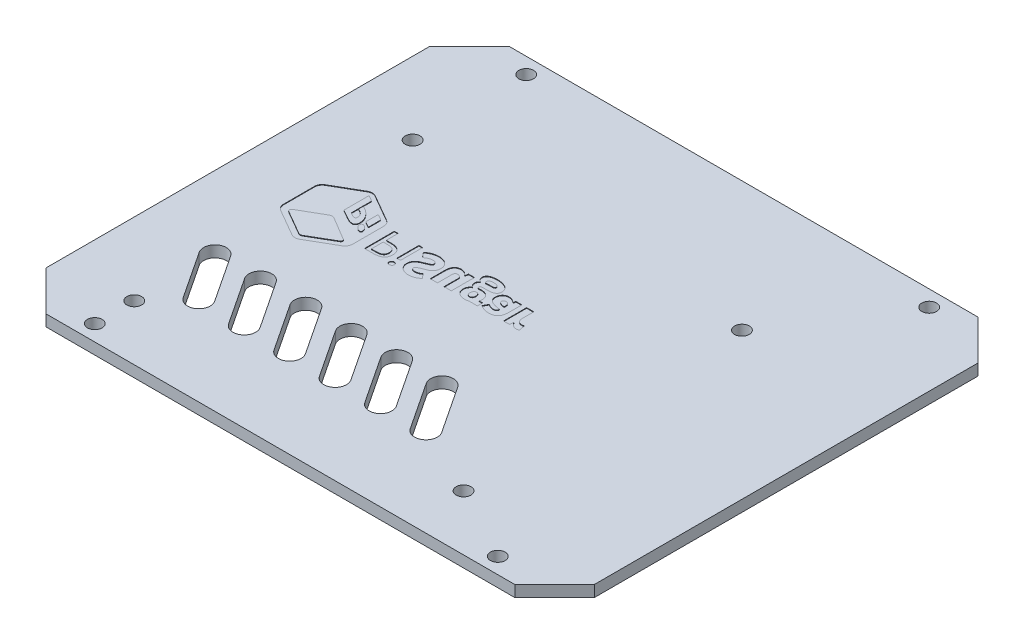
SolidWorks part; units mm, degrees
ref_plane "前视基准面" through (0, 0, 0) normal (0, 0, 1) x (1, 0, 0)
ref_plane "上视基准面" through (0, 0, 0) normal (0, 1, 0) x (1, 0, 0)
ref_plane "右视基准面" through (0, 0, 0) normal (1, 0, 0) x (0, 0, -1)
sketch "草图1" plane through (0, -19.39, 0) normal (0, -1, 0) x (1, 0, 0)
  line L16 (-51.8, -40.2958) -> (-44.7958, -47.3)
  line L17 (-44.7958, -47.3) -> (37.7958, -47.3)
  line L18 (37.7958, -47.3) -> (44.8, -40.2958)
  line L19 (44.8, -40.2958) -> (44.8, 27.2958)
  line L20 (44.8, 27.2958) -> (37.7958, 34.3)
  line L21 (-51.8, 27.2958) -> (-51.8, -40.2958)
  line L22 (37.7958, 34.3) -> (-44.7958, 34.3)
  line L23 (-44.7958, 34.3) -> (-51.8, 27.2958)
  line L24 (-51.8, -40.2958) -> (-44.7958, -47.3)
  line L25 (-44.7958, -47.3) -> (37.7958, -47.3)
  line L26 (37.7958, -47.3) -> (44.8, -40.2958)
  line L27 (44.8, -40.2958) -> (44.8, 27.2958)
  line L28 (44.8, 27.2958) -> (37.7958, 34.3)
  line L29 (-51.8, 27.2958) -> (-51.8, -40.2958)
  line L30 (37.7958, 34.3) -> (-44.7958, 34.3)
  line L31 (-44.7958, 34.3) -> (-51.8, 27.2958)
  dimension "D1" = 0.2
extrude "凸台-拉伸1" add sketch "草图1" along normal blind 2
sketch "草图2" plane through (0, -21.39, 0) normal (0, -1, 0) x (1, 0, 0)
  circle A0 centre (-39.0116, -24.5) radius 1.3
  circle A1 centre (19, -24.5) radius 1.3
  circle A2 centre (-39.0116, 24.5352) radius 1.3
  circle A3 centre (19, 24.5352) radius 1.3
  dimension "D1" = 2.6
extrude "切除-拉伸1" cut sketch "草图2" against normal up to next
sketch "草图3" plane through (0, -21.39, 0) normal (0, -1, 0) x (1, 0, 0)
  circle A0 centre (32, -44.5) radius 1.3 construction
  circle A1 centre (-39, -44.5) radius 1.3 construction
  circle A2 centre (32, 31.5) radius 1.3 construction
  circle A3 centre (-39, 31.5) radius 1.3 construction
  circle A4 centre (32, -44.5) radius 1.3
  circle A5 centre (-39, -44.5) radius 1.3
  circle A6 centre (32, 31.5) radius 1.3
  circle A7 centre (-39, 31.5) radius 1.3
extrude "切除-拉伸2" cut sketch "草图3" against normal up to next
sketch "草图4" plane through (0, -21.39, 0) normal (0, -1, 0) x (1, 0, 0)
  line L0 (-38.9928, 31.6194) -> (-39.0044, 24.6546) construction
  line L1 (-39.0282, 10.3) -> (-33.5143, 18.6425) construction
  line L2 (-40.6967, 11.4028) -> (-35.1828, 19.7453)
  line L3 (-37.3597, 9.1972) -> (-31.8458, 17.5397)
  line L5 (37.7958, 34.3) -> (-44.7958, 34.3) construction
  line L6 (-31.0282, 10.3) -> (-25.5143, 18.6425) construction
  line L9 (-32.6967, 11.4028) -> (-27.1828, 19.7453)
  line L12 (-29.3597, 9.1972) -> (-23.8458, 17.5397)
  line L15 (-23.0282, 10.3) -> (-17.5143, 18.6425) construction
  line L18 (-24.6967, 11.4028) -> (-19.1828, 19.7453)
  line L21 (-21.3597, 9.1972) -> (-15.8458, 17.5397)
  line L22 (-15.0282, 10.3) -> (-9.5143, 18.6425) construction
  line L23 (-16.6967, 11.4028) -> (-11.1828, 19.7453)
  line L24 (-13.3597, 9.1972) -> (-7.8458, 17.5397)
  line L25 (-7.0282, 10.3) -> (-1.5143, 18.6425) construction
  line L26 (-8.6967, 11.4028) -> (-3.1828, 19.7453)
  line L27 (-5.3597, 9.1972) -> (0.1542, 17.5397)
  line L28 (0.9718, 10.3) -> (6.4857, 18.6425) construction
  line L29 (-0.6967, 11.4028) -> (4.8172, 19.7453)
  line L30 (2.6403, 9.1972) -> (8.1542, 17.5397)
  arc A0 (-40.6967, 11.4028) -> (-37.3597, 9.1972) centre (-39.0282, 10.3) ccw
  arc A1 (-31.8458, 17.5397) -> (-35.1828, 19.7453) centre (-33.5143, 18.6425) ccw
  arc A12 (-32.6967, 11.4028) -> (-29.3597, 9.1972) centre (-31.0282, 10.3) ccw
  arc A13 (-23.8458, 17.5397) -> (-27.1828, 19.7453) centre (-25.5143, 18.6425) ccw
  arc A14 (-24.6967, 11.4028) -> (-21.3597, 9.1972) centre (-23.0282, 10.3) ccw
  arc A15 (-15.8458, 17.5397) -> (-19.1828, 19.7453) centre (-17.5143, 18.6425) ccw
  arc A16 (-16.6967, 11.4028) -> (-13.3597, 9.1972) centre (-15.0282, 10.3) ccw
  arc A17 (-7.8458, 17.5397) -> (-11.1828, 19.7453) centre (-9.5143, 18.6425) ccw
  arc A18 (-8.6967, 11.4028) -> (-5.3597, 9.1972) centre (-7.0282, 10.3) ccw
  arc A19 (0.1542, 17.5397) -> (-3.1828, 19.7453) centre (-1.5143, 18.6425) ccw
  arc A20 (-0.6967, 11.4028) -> (2.6403, 9.1972) centre (0.9718, 10.3) ccw
  arc A21 (8.1542, 17.5397) -> (4.8172, 19.7453) centre (6.4857, 18.6425) ccw
  point P6 (-36.2713, 14.4713)
  point P15 (-28.2713, 14.4713)
  point P22 (-20.2713, 14.4713)
  point P29 (-12.2713, 14.4713)
  point P36 (-4.2713, 14.4713)
  point P43 (3.7287, 14.4713)
  dimension "D1" = 2
  dimension "D2" = 10
  dimension "D3" = 5.5
  dimension "D4" = 12.8
  dimension "D5" = 24
  dimension "D6" = 6
extrude "切除-拉伸3" cut sketch "草图4" against normal up to next
sketch "草图5" plane through (0, -21.39, 0) normal (0, -1, 0) x (1, 0, 0)
  point P0 (-34.5006, 0.7543)
sketch_block_instance "块1-1"
sketch_block "块1"
sketch "草图6" plane through (0, -19.39, 0) normal (0, 1, 0) x (1, 0, 0)
  line L0 (-39.0322, 2.6968) -> (-34.8198, 0.2624) construction
  line L1 (-34.177, 0.2624) -> (-29.9873, 2.7014) construction
  line L2 (-29.9828, 3.2622) -> (-34.0539, 5.6966) construction
  line L3 (-29.6682, 9.5398) -> (-30.5435, 10.0367) construction
  line L4 (-30.6757, 9.9592) -> (-30.6757, 7.9487) construction
  line L5 (-30.6301, 7.8712) -> (-29.7548, 7.3788) construction
  line L6 (-29.6226, 7.4564) -> (-29.6226, 9.4623) construction
  line L7 (-33.3108, 9.1249) -> (-33.3108, 8.049) construction
  line L8 (-33.2652, 7.9715) -> (-32.8731, 7.7527) construction
  line L9 (-32.8458, 9.0109) -> (-33.2652, 9.2207) construction
  line L10 (-33.2652, 9.2207) -> (-33.2652, 10.0868) construction
  line L11 (-32.791, 9.8224) -> (-33.2652, 10.0868) construction
  line L12 (-34.3274, 7.7345) -> (-32.823, 6.8819) construction
  line L13 (-34.373, 12.0335) -> (-34.373, 7.8119) construction
  line L14 (-33.3563, 11.6095) -> (-34.2408, 12.111) construction
  line L15 (-33.3108, 10.1644) -> (-33.3108, 11.532) construction
  line L16 (-33.3108, 9.1249) -> (-33.3108, 10.1644) construction
  line L17 (-17.9609, 5.9474) -> (-18.6265, 5.6829) construction
  line L18 (-17.7011, 5.0538) -> (-17.0627, 4.2514) construction
  line L19 (-19.6477, 6.6221) -> (-18.9684, 6.9093) construction
  line L20 (-20.2085, 7.429) -> (-20.9333, 8.3134) construction
  line L21 (-10.1469, 9.1523) -> (-9.7593, 9.1523) construction
  line L22 (-5.5196, 7.1144) -> (-5.5196, 7.7664) construction
  line L23 (-26.0439, 6.3576) -> (-26.0439, 4.2651) construction
  line L24 (-26.0439, 4.2651) -> (-25.2871, 4.2651) construction
  line L25 (-25.2597, 6.3576) -> (-26.0439, 6.3576) construction
  line L26 (-26.7095, 3.7272) -> (-26.7095, 8.979) construction
  line L27 (-26.7095, 8.979) -> (-26.0439, 8.979) construction
  line L28 (-26.0439, 8.979) -> (-26.0439, 6.8956) construction
  line L29 (-26.0439, 6.8956) -> (-25.1731, 6.8956) construction
  line L30 (-25.2096, 3.7272) -> (-26.7095, 3.7272) construction
  line L31 (-33.1558, -0.189) -> (-33.8122, -0.5719) construction
  line L32 (-35.189, -0.5719) -> (-35.8455, -0.189) construction
  line L33 (-35.8455, -0.189) -> (-39.2511, 1.7759) construction
  line L34 (-39.2511, 1.7759) -> (-39.9076, 2.1543) construction
  line L35 (-40.596, 3.3442) -> (-40.596, 8.7967) construction
  line L36 (-39.9076, 9.9866) -> (-39.2511, 10.365) construction
  line L37 (-39.2511, 10.365) -> (-35.8455, 12.3299) construction
  line L38 (-35.8455, 12.3299) -> (-35.189, 12.7128) construction
  line L39 (-33.8122, 12.7128) -> (-33.1558, 12.3299) construction
  line L40 (-33.1558, 12.3299) -> (-29.7503, 10.365) construction
  line L41 (-29.7503, 10.365) -> (-29.0938, 9.9866) construction
  line L42 (-28.4054, 8.7967) -> (-28.4054, 3.3442) construction
  line L43 (-29.0938, 2.1543) -> (-29.7503, 1.7759) construction
  line L44 (-29.7503, 1.7759) -> (-33.1558, -0.189) construction
  line L45 (-5.3737, 8.5687) -> (-5.2826, 8.979) construction
  line L46 (-5.2826, 8.979) -> (-4.2431, 8.979) construction
  line L47 (-4.2431, 8.979) -> (-4.2431, 6.6631) construction
  line L48 (-7.6486, 5.3365) -> (-7.2018, 6.1753) construction
  line L49 (-5.4056, 8.5687) -> (-5.3737, 8.5687) construction
  line L50 (-8.0133, 5.8243) -> (-8.0133, 4.9034) construction
  line L51 (-8.0133, 4.9034) -> (-9.5086, 4.9034) construction
  line L52 (-11.3094, 7.3378) -> (-11.3094, 7.3652) construction
  line L53 (-11.3869, 8.8286) -> (-11.3869, 8.8651) construction
  line L54 (-9.5178, 8.1767) -> (-10.1606, 8.1767) construction
  line L55 (-8.6424, 5.8243) -> (-8.0133, 5.8243) construction
  line L56 (-13.8761, 4.9034) -> (-13.8761, 7.5749) construction
  line L57 (-15.0295, 7.2649) -> (-15.0295, 4.9034) construction
  line L58 (-15.0295, 4.9034) -> (-16.3014, 4.9034) construction
  line L59 (-16.3014, 4.9034) -> (-16.3014, 7.4245) construction
  line L60 (-13.7575, 8.4183) -> (-13.7302, 8.4183) construction
  line L61 (-13.7302, 8.4183) -> (-13.639, 8.979) construction
  line L62 (-13.639, 8.979) -> (-12.5996, 8.979) construction
  line L63 (-12.5996, 8.979) -> (-12.5996, 4.9034) construction
  line L64 (-12.5996, 4.9034) -> (-13.8761, 4.9034) construction
  line L65 (-21.7265, 8.979) -> (-21.7265, 5.0857) construction
  line L66 (-22.3785, 8.979) -> (-21.7265, 8.979) construction
  line L67 (-22.3785, 5.0857) -> (-22.3785, 8.979) construction
  line L68 (-21.7265, 5.0857) -> (-22.3785, 5.0857) construction
  line L69 (-3.4042, 8.979) -> (-2.1368, 8.979) construction
  line L70 (-2.1368, 8.979) -> (-2.1368, 6.6494) construction
  line L71 (-0.8102, 5.9838) -> (-0.596, 4.8851) construction
  line L72 (-2.2508, 5.61) -> (-2.2782, 5.61) construction
  line L73 (-2.2782, 5.61) -> (-2.3648, 4.9034) construction
  line L74 (-2.3648, 4.9034) -> (-3.4042, 4.9034) construction
  line L75 (-3.4042, 4.9034) -> (-3.4042, 8.979) construction
  line L76 (-39.0322, 2.6968) -> (-34.8198, 0.2624)
  line L77 (-34.177, 0.2624) -> (-29.9873, 2.7014)
  line L78 (-29.9828, 3.2622) -> (-34.0539, 5.6966)
  line L79 (-29.6682, 9.5398) -> (-30.5435, 10.0367)
  line L80 (-30.6757, 9.9592) -> (-30.6757, 7.9487)
  line L81 (-30.6301, 7.8712) -> (-29.7548, 7.3788)
  line L82 (-29.6226, 7.4564) -> (-29.6226, 9.4623)
  line L83 (-33.3108, 9.1249) -> (-33.3108, 8.049)
  line L84 (-33.2652, 7.9715) -> (-32.8731, 7.7527)
  line L85 (-32.8458, 9.0109) -> (-33.2652, 9.2207)
  line L86 (-33.2652, 9.2207) -> (-33.2652, 10.0868)
  line L87 (-32.791, 9.8224) -> (-33.2652, 10.0868)
  line L88 (-34.3274, 7.7345) -> (-32.823, 6.8819)
  line L89 (-34.373, 12.0335) -> (-34.373, 7.8119)
  line L90 (-33.3563, 11.6095) -> (-34.2408, 12.111)
  line L91 (-33.3108, 10.1644) -> (-33.3108, 11.532)
  line L92 (-33.3108, 9.1249) -> (-33.3108, 10.1644)
  line L93 (-17.9609, 5.9474) -> (-18.6265, 5.6829)
  line L94 (-17.7011, 5.0538) -> (-17.0627, 4.2514)
  line L95 (-19.6477, 6.6221) -> (-18.9684, 6.9093)
  line L96 (-20.2085, 7.429) -> (-20.9333, 8.3134)
  line L97 (-10.1469, 9.1523) -> (-9.7593, 9.1523)
  line L98 (-5.5196, 7.1144) -> (-5.5196, 7.7664)
  line L99 (-26.0439, 6.3576) -> (-26.0439, 4.2651)
  line L100 (-26.0439, 4.2651) -> (-25.2871, 4.2651)
  line L101 (-25.2597, 6.3576) -> (-26.0439, 6.3576)
  line L102 (-26.7095, 3.7272) -> (-26.7095, 8.979)
  line L103 (-26.7095, 8.979) -> (-26.0439, 8.979)
  line L104 (-26.0439, 8.979) -> (-26.0439, 6.8956)
  line L105 (-26.0439, 6.8956) -> (-25.1731, 6.8956)
  line L106 (-25.2096, 3.7272) -> (-26.7095, 3.7272)
  line L107 (-33.1558, -0.189) -> (-33.8122, -0.5719)
  line L108 (-35.189, -0.5719) -> (-35.8455, -0.189)
  line L109 (-35.8455, -0.189) -> (-39.2511, 1.7759)
  line L110 (-39.2511, 1.7759) -> (-39.9076, 2.1543)
  line L111 (-40.596, 3.3442) -> (-40.596, 8.7967)
  line L112 (-39.9076, 9.9866) -> (-39.2511, 10.365)
  line L113 (-39.2511, 10.365) -> (-35.8455, 12.3299)
  line L114 (-35.8455, 12.3299) -> (-35.189, 12.7128)
  line L115 (-33.8122, 12.7128) -> (-33.1558, 12.3299)
  line L116 (-33.1558, 12.3299) -> (-29.7503, 10.365)
  line L117 (-29.7503, 10.365) -> (-29.0938, 9.9866)
  line L118 (-28.4054, 8.7967) -> (-28.4054, 3.3442)
  line L119 (-29.0938, 2.1543) -> (-29.7503, 1.7759)
  line L120 (-29.7503, 1.7759) -> (-33.1558, -0.189)
  line L121 (-5.3737, 8.5687) -> (-5.2826, 8.979)
  line L122 (-5.2826, 8.979) -> (-4.2431, 8.979)
  line L123 (-4.2431, 8.979) -> (-4.2431, 6.6631)
  line L124 (-7.6486, 5.3365) -> (-7.2018, 6.1753)
  line L125 (-5.4056, 8.5687) -> (-5.3737, 8.5687)
  line L126 (-8.0133, 5.8243) -> (-8.0133, 4.9034)
  line L127 (-8.0133, 4.9034) -> (-9.5086, 4.9034)
  line L128 (-11.3094, 7.3378) -> (-11.3094, 7.3652)
  line L129 (-11.3869, 8.8286) -> (-11.3869, 8.8651)
  line L130 (-9.5178, 8.1767) -> (-10.1606, 8.1767)
  line L131 (-8.6424, 5.8243) -> (-8.0133, 5.8243)
  line L132 (-13.8761, 4.9034) -> (-13.8761, 7.5749)
  line L133 (-15.0295, 7.2649) -> (-15.0295, 4.9034)
  line L134 (-15.0295, 4.9034) -> (-16.3014, 4.9034)
  line L135 (-16.3014, 4.9034) -> (-16.3014, 7.4245)
  line L136 (-13.7575, 8.4183) -> (-13.7302, 8.4183)
  line L137 (-13.7302, 8.4183) -> (-13.639, 8.979)
  line L138 (-13.639, 8.979) -> (-12.5996, 8.979)
  line L139 (-12.5996, 8.979) -> (-12.5996, 4.9034)
  line L140 (-12.5996, 4.9034) -> (-13.8761, 4.9034)
  line L141 (-21.7265, 8.979) -> (-21.7265, 5.0857)
  line L142 (-22.3785, 8.979) -> (-21.7265, 8.979)
  line L143 (-22.3785, 5.0857) -> (-22.3785, 8.979)
  line L144 (-21.7265, 5.0857) -> (-22.3785, 5.0857)
  line L145 (-3.4042, 8.979) -> (-2.1368, 8.979)
  line L146 (-2.1368, 8.979) -> (-2.1368, 6.6494)
  line L147 (-0.8102, 5.9838) -> (-0.596, 4.8851)
  line L148 (-2.2508, 5.61) -> (-2.2782, 5.61)
  line L149 (-2.2782, 5.61) -> (-2.3648, 4.9034)
  line L150 (-2.3648, 4.9034) -> (-3.4042, 4.9034)
  line L151 (-3.4042, 4.9034) -> (-3.4042, 8.979)
  spline S0 degree 3 poles (1947.2043, 259.0221) (-2040.5975, -86.3945) (1971.5647, -86.1046) (-2015.9835, 259.8919) knots -24.014283 -24.014283 -24.014283 -24.014283 31.060476 31.060476 31.060476 31.060476 only from (-34.8198, 0.2624) to (-34.177, 0.2624) construction
  spline S1 degree 3 poles (-178.8618, 1996.4067) (-13.3017, -2002.4803) (85.7628, 2005.1657) (-277.1173, -1980.6649) knots -12.069605 -12.069605 -12.069605 -12.069605 23.053377 23.053377 23.053377 23.053377 only from (-29.9873, 2.7014) to (-29.9828, 3.2622) construction
  spline S2 degree 3 poles (-2011.9647, -280.5218) (1973.0796, 101.2598) (-2042.0834, 101.2623) (1942.99, -280.5143) knots -16.956312 -16.956312 -16.956312 -16.956312 31.955994 31.955994 31.955994 31.955994 only from (-34.0539, 5.6966) to (-34.9429, 5.6966) construction
  spline S3 degree 2 poles (1696.8938, 1005.9909) (-1772.9636, -998.1959) (1692.7429, 1003.6514) knots -19.544322 -19.544322 -19.544322 21.524182 21.524182 21.524182 only from (-34.9429, 5.6966) to (-39.0732, 3.3123) construction
  spline S4 degree 3 poles (312.9236, -1964.6822) (-255.5836, 1997.2947) (39.8207, -2001.4292) (20.6091, 2000.9771) knots -16.033039 -16.033039 -16.033039 -16.033039 19.060221 19.060221 19.060221 19.060221 only from (-39.0732, 3.3123) to (-39.0322, 2.6968) construction
  spline S5 degree 3 poles (1612.1466, 1139.1382) (-173.749, 124.6775) (-29.5451, -1.4055) (-29.5451, 6.2482) (-29.5451, 12.5795) (-131.1047, 41.0713) (891.7703, -1766.7786) knots -20.983072 -20.983072 -20.983072 -20.983072 3 3 3 23.1269 23.1269 23.1269 23.1269 only from (-30.1469, 6.0431) to (-30.1469, 7.1281) construction
  spline S6 degree 3 poles (-1593.6748, -1232.4433) (112.4759, -108.2288) (-30.7532, 14.45) (-30.7532, 6.9321) (-30.7532, 0.2328) (76.6581, -24.0346) (-1002.5668, 1752.6044) knots -22.899222 -22.899222 -22.899222 -22.899222 1 1 1 21.696321 21.696321 21.696321 21.696321 only from (-30.1469, 7.1281) to (-30.1469, 6.0431) construction
  spline S7 degree 3 poles (-1735.267, -1035.1971) (1720.3132, 981.2712) (-1822.079, -884.2768) (1795.5461, 824.5182) knots -24.864003 -24.864003 -24.864003 -24.864003 29.805716 29.805716 29.805716 29.805716 only from (-30.5435, 10.0367) to (-30.6757, 9.9592) construction
  spline S8 degree 3 poles (1803.8452, -787.8206) (-1835.1338, 879.7734) (1736.3613, -937.8925) (-1752.2845, 1025.0132) knots -52.644856 -52.644856 -52.644856 -52.644856 63.422153 63.422153 63.422153 63.422153 only from (-30.6757, 7.9487) to (-30.6301, 7.8712) construction
  spline S9 degree 3 poles (1675.9971, 1050.9308) (-1781.5786, -962.103) (1762.6814, 899.8753) (-1856.6746, -805.2277) knots -20.869425 -20.869425 -20.869425 -20.869425 33.809897 33.809897 33.809897 33.809897 only from (-29.7548, 7.3788) to (-29.6226, 7.4564) construction
  spline S10 degree 3 poles (-1017.153, 1748.416) (898.1967, -1765.8691) (-895.3334, 1815.971) (771.5167, -1822.726) knots -45.73326 -45.73326 -45.73326 -45.73326 46.535072 46.535072 46.535072 46.535072 only from (-29.6226, 9.4623) to (-29.6682, 9.5398) construction
  spline S11 degree 3 poles (1241.4728, -1544.2848) (-126.4363, -19.7603) (-21.5989, 9.5171) (-21.5989, 3.8639) (-21.5989, -3.1211) (-150.7291, 66.7677) (1747.5616, 931.244) knots -20.398043 -20.398043 -20.398043 -20.398043 3 3 3 28.967808 28.967808 28.967808 28.967808 only from (-22.0502, 4.2833) to (-22.0502, 3.44) construction
  spline S12 degree 3 poles (-1791.638, 931.233) (106.6275, 66.7672) (-22.5016, -3.1211) (-22.5016, 3.8639) (-22.5016, 9.5171) (82.3355, -19.7602) (-1285.567, -1544.2778) knots -24.967698 -24.967698 -24.967698 -24.967698 1 1 1 24.398007 24.398007 24.398007 24.398007 only from (-22.0502, 3.44) to (-22.0502, 4.2833) construction
  spline S13 degree 3 poles (953.112, -1731.5311) (-960.0271, 1783.9495) (831.3079, -1798.9714) (-833.3757, 1840.6921) knots -41.715469 -41.715469 -41.715469 -41.715469 50.515238 50.515238 50.515238 50.515238 only from (-33.3108, 8.049) to (-33.2652, 7.9715) construction
  spline S14 degree 3 poles (345.3515, -1953.7628) (-656.074, 2008.4671) (704.4049, -1945.0024) (-795.7723, 1856.1671) knots -18.836401 -18.836401 -18.836401 -18.836401 26.867419 26.867419 26.867419 26.867419 only from (-32.8731, 7.7527) to (-32.0799, 7.9031) construction
  spline S15 degree 3 poles (393.8329, 1947.428) (-1017.3565, -1766.8215) (1294.138, 1559.3727) (-1541.9229, -1298.5467) knots -37.738435 -37.738435 -37.738435 -37.738435 30.849118 30.849118 30.849118 30.849118 only from (-32.0799, 7.9031) to (-32.8458, 9.0109) construction
  spline S16 degree 3 poles (-1970.6267, 490.4514) (1900.3877, -652.3893) (-1909.3139, 822.203) (1735.9268, -921.8099) knots -2.984455 -2.984455 -2.984455 -2.984455 24.908291 24.908291 24.908291 24.908291 only from (-31.0405, 7.315) to (-32.791, 9.8224) construction
  spline S17 degree 3 poles (1301.0551, -1483.1694) (-1380.7778, 1570.3517) (1272.9624, -1585.6466) (-1251.2088, 1591.7607) knots -4.177868 -4.177868 -4.177868 -4.177868 21.267464 21.267464 21.267464 21.267464 only from (-32.823, 6.8819) to (-31.0405, 7.315) construction
  spline S18 degree 3 poles (-426.7908, -1953.0944) (416.9018, 1960.3516) (-543.6183, -1930.3492) (531.9657, 1925.7159) knots -40.574336 -40.574336 -40.574336 -40.574336 54.224541 54.224541 54.224541 54.224541 only from (-34.373, 7.8119) to (-34.3274, 7.7345) construction
  spline S19 degree 3 poles (-1739.7201, -1031.8845) (1717.3311, 982.0362) (-1826.4475, -880.8273) (1792.473, 825.1567) knots -21.867988 -21.867988 -21.867988 -21.867988 32.80886 32.80886 32.80886 32.80886 only from (-34.2408, 12.111) to (-34.373, 12.0335) construction
  spline S20 degree 3 poles (1326.5597, 1477.8337) (-1443.7748, -1422.5109) (1417.5131, 1403.8248) (-1515.2659, -1331.1895) knots -66.611259 -66.611259 -66.611259 -66.611259 68.63044 68.63044 68.63044 68.63044 only from (-33.3108, 11.532) to (-33.3563, 11.6095) construction
  spline S21 degree 3 poles (-1127.9465, 1668.9065) (1205.0665, -1581.8003) (-1320.6139, 1532.1331) (1326.4072, -1474.1074) knots -17.356672 -17.356672 -17.356672 -17.356672 19.212167 19.212167 19.212167 19.212167 only from (-18.6265, 5.6829) to (-19.4334, 5.0857) construction
  spline S22 degree 3 poles (1945.6237, -352.8331) (-1917.2958, 619.5498) (1753.4488, -897.6325) (-1594.6226, 1226.9154) knots -23.773694 -23.773694 -23.773694 -23.773694 31.399142 31.399142 31.399142 31.399142 only from (-19.4334, 5.0857) to (-18.7952, 4.6435) construction
  spline S23 degree 3 poles (-1957.8604, 491.3787) (1905.2875, -332.0334) (-1960.1859, 166.6666) (1980.2936, 44.6676) knots -22.175827 -22.175827 -22.175827 -22.175827 30.019969 30.019969 30.019969 30.019969 only from (-18.7952, 4.6435) to (-17.7011, 5.0538) construction
  spline S24 degree 3 poles (-1996.9289, 274.3391) (2008.3741, -55.5657) (-2041.9478, -141.8187) (1949.9756, 346.3582) knots -14.985955 -14.985955 -14.985955 -14.985955 26.624596 26.624596 26.624596 26.624596 only from (-17.0627, 4.2514) to (-18.7952, 3.5448) construction
  spline S25 degree 3 poles (-959.5674, 1764.5293) (1176.2874, -1603.5878) (-1432.6495, 1427.6748) (1567.7803, -1205.173) knots -7.558703 -7.558703 -7.558703 -7.558703 20.482777 20.482777 20.482777 20.482777 only from (-18.7952, 3.5448) to (-20.7327, 5.1587) construction
  spline S26 degree 3 poles (1924.0493, -458.54) (-2016.5165, 343.495) (1995.4741, -211.501) (-2016.1303, 116.1959) knots -7.852621 -7.852621 -7.852621 -7.852621 24.144848 24.144848 24.144848 24.144848 only from (-20.7327, 5.1587) to (-19.6477, 6.6221) construction
  spline S27 degree 3 poles (615.0637, -1888.8545) (-795.6899, 1841.0297) (868.9978, -1778.6578) (-986.0957, 1757.28) knots -9.138526 -9.138526 -9.138526 -9.138526 27.25787 27.25787 27.25787 27.25787 only from (-18.9684, 6.9093) to (-18.2162, 7.5111) construction
  spline S28 degree 3 poles (215.7009, 1986.9997) (-654.6592, -1923.8751) (894.6606, 1828.6602) (-1110.216, -1665.8008) knots -22.542702 -22.542702 -22.542702 -22.542702 37.658646 37.658646 37.658646 37.658646 only from (-18.2162, 7.5111) to (-18.9137, 7.9761) construction
  spline S29 degree 3 poles (-1605.429, -1208.7716) (1666.7814, 1140.7416) (-1773.5402, -1019.3674) (1765.9801, 905.5471) knots -8.791084 -8.791084 -8.791084 -8.791084 32.386114 32.386114 32.386114 32.386114 only from (-18.9137, 7.9761) to (-20.2085, 7.429) construction
  spline S30 degree 3 poles (1966.5787, -197.5818) (-2051.7497, -0.967) (2002.48, 224.4874) (-1974.8286, -400.794) knots -6.294928 -6.294928 -6.294928 -6.294928 33.756853 33.756853 33.756853 33.756853 only from (-20.9333, 8.3134) to (-18.9411, 9.0793) construction
  spline S31 degree 3 poles (124.1341, -1982.3989) (-457.1442, 1958.1164) (708.8959, -1855.2284) (-1015.0804, 1736.3895) knots 0.697384 0.697384 0.697384 0.697384 28.978211 28.978211 28.978211 28.978211 only from (-18.9411, 9.0793) to (-16.9033, 7.4108) construction
  spline S32 degree 3 poles (-1495.2544, 1354.2838) (1523.5493, -1377.9736) (-1538.1686, 1424.3054) (1353.4505, -1448.6746) knots -4.734801 -4.734801 -4.734801 -4.734801 40.265101 40.265101 40.265101 40.265101 only from (-16.9033, 7.4108) to (-17.9609, 5.9474) construction
  spline S33 degree 3 poles (-1961.8056, -418.0731) (126.6492, -101.6131) (-10.6711, 16.7967) (-10.6711, 6.2847) (-10.6711, -3.9538) (125.3735, 107.9903) (-1932.7785, 547.0377) knots -21.79377 -21.79377 -21.79377 -21.79377 3 3 3 27.67833 27.67833 27.67833 27.67833 only from (-10.156, 6.923) to (-10.156, 5.6556) construction
  spline S34 degree 3 poles (1882.1607, 641.7029) (-158.572, 123.862) (-9.6409, -4.6535) (-9.6409, 6.2847) (-9.6409, 17.5385) (-160.5965, -118.9677) (1923.9331, -488.0552) knots -25.364902 -25.364902 -25.364902 -25.364902 1 1 1 27.543492 27.543492 27.543492 27.543492 only from (-10.156, 5.6556) to (-10.156, 6.923) construction
  spline S35 degree 3 poles (398.3769, -1946.8651) (-621.0655, 1916.7975) (746.5301, -1849.6014) (-860.4662, 1818.6943) knots -20.367991 -20.367991 -20.367991 -20.367991 27.043685 27.043685 27.043685 27.043685 only from (-9.7593, 9.1523) to (-9.1667, 9.4441) construction
  spline S36 degree 3 poles (-1851.6901, 784.2948) (1770.8918, -932.7585) (-1685.1957, 1125.6418) (1512.1872, -1283.8884) knots -14.155704 -14.155704 -14.155704 -14.155704 26.455766 26.455766 26.455766 26.455766 only from (-9.1667, 9.4441) to (-10.0557, 9.8954) construction
  spline S37 degree 3 poles (-1999.7746, -177.9397) (2048.5506, 17.7992) (-2059.7856, 149.4036) (1971.6374, -249.0633) knots -24.53604 -24.53604 -24.53604 -24.53604 22.203045 22.203045 22.203045 22.203045 only from (-10.0557, 9.8954) to (-10.9219, 9.4668) construction
  spline S38 degree 3 poles (335.4233, 1977.3974) (-130.5762, -1935.4278) (-138.8194, 1950.0115) (386.7962, -1948.2187) knots -42.090152 -42.090152 -42.090152 -42.090152 46.007634 46.007634 46.007634 46.007634 only from (-10.9219, 9.4668) to (-10.7304, 9.1021) construction
  spline S39 degree 3 poles (-2000.164, -195.6542) (1968.231, 177.2652) (-1992.5781, -127.132) (1986.8184, 117.9013) knots -23.761314 -23.761314 -23.761314 -23.761314 27.411452 27.411452 27.411452 27.411452 only from (-10.7304, 9.1021) to (-10.1469, 9.1523) construction
  spline S40 degree 3 poles (1900.4815, 611.268) (-1853.5024, -713.4995) (1804.2956, 824.4669) (-1796.5625, -882.5407) knots -25.691977 -25.691977 -25.691977 -25.691977 25.491412 25.491412 25.491412 25.491412 only from (-5.5196, 7.7664) to (-6.135, 8.09) construction
  spline S41 degree 3 poles (-2003.4629, -52.8338) (2017.9029, -136.2777) (-2009.5197, 324.3726) (1939.2706, -450.8338) knots -29.27083 -29.27083 -29.27083 -29.27083 28.779665 28.779665 28.779665 28.779665 only from (-6.135, 8.09) to (-6.5727, 7.739) construction
  spline S42 degree 3 poles (-1965.4656, -395.4958) (1971.7383, 441.6954) (-1983.3474, -426.4496) (1951.4791, 419.1184) knots -18.272249 -18.272249 -18.272249 -18.272249 20.366917 20.366917 20.366917 20.366917 only from (-6.5727, 7.739) to (-5.5196, 7.1144) construction
  spline S43 degree 3 poles (-552.3477, -1916.0072) (39.6444, 1949.1893) (231.1798, -1947.9287) (-488.2476, 1949.0672) knots -16.951569 -16.951569 -16.951569 -16.951569 21.292276 21.292276 21.292276 21.292276 only from (-25.2871, 4.2651) to (-23.9011, 5.2681) construction
  spline S44 degree 3 poles (74.9674, -1978.7796) (-669.1868, 1491.4113) (1220.9961, -1007.5518) (-1925.4997, 576.7533) knots -20.703775 -20.703775 -20.703775 -20.703775 29.911591 29.911591 29.911591 29.911591 only from (-23.9011, 5.2681) to (-25.2597, 6.3576) construction
  spline S45 degree 3 poles (1967.7044, -102.3152) (-2083.6001, -202.2982) (1987.7708, 465.393) (-1913.3422, -643.1952) knots -12.662635 -12.662635 -12.662635 -12.662635 20.708978 20.708978 20.708978 20.708978 only from (-25.1731, 6.8956) to (-23.2401, 5.2681) construction
  spline S46 degree 3 poles (-1462.7137, 1393.5071) (1511.2501, -1404.3078) (-1580.4996, 1407.0991) (1432.7296, -1365.1759) knots -7.615095 -7.615095 -7.615095 -7.615095 23.693651 23.693651 23.693651 23.693651 only from (-23.2401, 5.2681) to (-25.2096, 3.7272) construction
  spline S47 degree 3 poles (-1986.2159, -424.6605) (1872.5149, 650.7296) (-1856.7008, -859.0204) (1668.1443, 1044.8861) knots -40.403395 -40.403395 -40.403395 -40.403395 46.454358 46.454358 46.454358 46.454358 only from (-33.8122, -0.5719) to (-34.5006, -0.7543) construction
  spline S48 degree 3 poles (-1740.3489, 1039.5921) (1790.0962, -854.0172) (-1943.0897, 646.2372) (1918.0006, -420.927) knots -38.373718 -38.373718 -38.373718 -38.373718 48.302597 48.302597 48.302597 48.302597 only from (-34.5006, -0.7543) to (-35.189, -0.5719) construction
  spline S49 degree 3 poles (-754.8971, 1867.8409) (885.9932, -1784.6) (-1157.7277, 1677.1962) (1246.9181, -1524.5355) knots -12.834285 -12.834285 -12.834285 -12.834285 29.798641 29.798641 29.798641 29.798641 only from (-39.9076, 2.1543) to (-40.596, 3.3442) construction
  spline S50 degree 3 poles (1310.7611, 1480.2732) (-1219.4015, -1620.1293) (943.9093, 1763.7167) (-807.2491, -1834.6442) knots -11.169927 -11.169927 -11.169927 -11.169927 32.277267 32.277267 32.277267 32.277267 only from (-40.596, 8.7967) to (-39.9076, 9.9866) construction
  spline S51 degree 3 poles (1829.5545, -704.5958) (-1983.3127, 518.655) (1959.6502, -271.0062) (-2031.7382, 64.4568) knots -28.630568 -28.630568 -28.630568 -28.630568 59.634843 59.634843 59.634843 59.634843 only from (-35.189, 12.7128) to (-34.5006, 12.8952) construction
  spline S52 degree 3 poles (1962.7022, 65.7414) (-2028.2181, -273.3756) (1913.3784, 521.8911) (-1897.0742, -708.4939) knots -29.74703 -29.74703 -29.74703 -29.74703 58.724161 58.724161 58.724161 58.724161 only from (-34.5006, 12.8952) to (-33.8122, 12.7128) construction
  spline S53 degree 3 poles (611.3262, -1882.3455) (-897.4898, 1821.8566) (1049.2417, -1687.0258) (-1295.1838, 1553.5314) knots -2.467628 -2.467628 -2.467628 -2.467628 41.506639 41.506639 41.506639 41.506639 only from (-29.0938, 9.9866) to (-28.4054, 8.7967) construction
  spline S54 degree 3 poles (-1230.5684, -1592.4268) (988.9215, 1738.3623) (-842.904, -1836.9675) (564.0724, 1910.0048) knots -0.095652 -0.095652 -0.095652 -0.095652 42.997123 42.997123 42.997123 42.997123 only from (-28.4054, 3.3442) to (-29.0938, 2.1543) construction
  spline S55 degree 3 poles (-1430.5573, 1407.5659) (1723.1127, -1481.9909) (-1919.6145, 1389.7982) (1763.4855, -917.7581) knots -7.107453 -7.107453 -7.107453 -7.107453 39.300169 39.300169 39.300169 39.300169 only from (-4.2431, 6.6631) to (-5.8934, 4.8031) construction
  spline S56 degree 3 poles (200.3126, 1993.6618) (-113.4143, -2029.6162) (37.9701, 2047.0917) (-46.8978, -1994.2146) knots -24.475698 -24.475698 -24.475698 -24.475698 28.452112 28.452112 28.452112 28.452112 only from (-5.8934, 4.8031) to (-7.6486, 5.3365) construction
  spline S57 degree 3 poles (-1933.6669, -520.0604) (1769.2026, 770.3694) (-1678.914, -975.8177) (1607.9896, 1184.3814) knots -29.345565 -29.345565 -29.345565 -29.345565 33.949512 33.949512 33.949512 33.949512 only from (-7.2018, 6.1753) to (-6.135, 5.8197) construction
  spline S58 degree 3 poles (-1709.7987, 1053.3931) (1749.403, -1046.8479) (-1793.7464, 1008.7473) (1793.1121, -866.6254) knots -20.675466 -20.675466 -20.675466 -20.675466 32.208493 32.208493 32.208493 32.208493 only from (-6.135, 5.8197) to (-5.5196, 6.3394) construction
  spline S59 degree 3 poles (1975.7527, -248.8039) (-1868.9813, 512.6632) (1631.6647, -894.331) (-1295.7423, 1512.4535) knots -12.733532 -12.733532 -12.733532 -12.733532 25.757539 25.757539 25.757539 25.757539 only from (-5.5196, 6.3394) to (-7.7854, 7.8393) construction
  spline S60 degree 3 poles (1042.4421, 1706.8309) (-834.6219, -1820.7719) (589.0356, 1925.2458) (-367.8223, -1955.7065) knots -11.03402 -11.03402 -11.03402 -11.03402 21.264003 21.264003 21.264003 21.264003 only from (-7.7854, 7.8393) to (-6.5727, 9.0793) construction
  spline S61 degree 3 poles (-582.1125, -1906.1013) (523.4678, 1965.3983) (-513.1262, -1956.0805) (513.8823, 1939.9285) knots -17.627726 -17.627726 -17.627726 -17.627726 33.245267 33.245267 33.245267 33.245267 only from (-6.5727, 9.0793) to (-5.4056, 8.5687) construction
  spline S62 degree 3 poles (-1930.5691, 559.3395) (1974.8488, -448.3348) (-2018.9786, 347.7304) (1976.7281, -218.5664) knots -33.500705 -33.500705 -33.500705 -33.500705 55.20773 55.20773 55.20773 55.20773 only from (-9.5086, 4.9034) to (-10.156, 4.8031) construction
  spline S63 degree 3 poles (-1999.2913, 198.6019) (2020.2524, -1.5641) (-2032.1384, -171.0059) (1955.7763, 357.6437) knots -3.872904 -3.872904 -3.872904 -3.872904 23.676976 23.676976 23.676976 23.676976 only from (-10.156, 4.8031) to (-11.8611, 6.2847) construction
  spline S64 degree 3 poles (1939.5115, 440.407) (-1940.4923, -577.4399) (1873.7743, 723.7895) (-1830.7521, -821.4821) knots -8.023341 -8.023341 -8.023341 -8.023341 31.752387 31.752387 31.752387 31.752387 only from (-11.8611, 6.2847) to (-11.3094, 7.3378) construction
  spline S65 degree 3 poles (-1329.9726, 1509.8665) (1428.2205, -1408.3534) (-1547.8279, 1317.3332) (1597.8765, -1177.5524) knots -10.762319 -10.762319 -10.762319 -10.762319 36.904963 36.904963 36.904963 36.904963 only from (-11.3094, 7.3652) to (-11.7608, 8.1265) construction
  spline S66 degree 3 poles (1690.5146, -1041.4074) (-1758.3489, 1014.3497) (1757.9984, -959.3158) (-1776.7351, 948.7003) knots -9.879735 -9.879735 -9.879735 -9.879735 41.23424 41.23424 41.23424 41.23424 only from (-11.7608, 8.1265) to (-11.3869, 8.8286) construction
  spline S67 degree 3 poles (-752.9374, 1842.3255) (1308.8718, -1353.5914) (-1702.759, 958.5145) (1892.0914, -582.47) knots -26.637538 -26.637538 -26.637538 -26.637538 53.487657 53.487657 53.487657 53.487657 only from (-11.3869, 8.8651) to (-11.9659, 9.6674) construction
  spline S68 degree 3 poles (1894.089, -594.3405) (-1996.6922, 519.1508) (2004.2706, -389.5025) (-1990.0486, 289.9866) knots 3.488718 3.488718 3.488718 3.488718 33.266204 33.266204 33.266204 33.266204 only from (-11.9659, 9.6674) to (-10.2563, 10.6932) construction
  spline S69 degree 3 poles (883.5316, -1769.7092) (-1265.933, 1528.3806) (1531.048, -1233.7757) (-1756.2499, 971.1381) knots 2.502912 2.502912 2.502912 2.502912 33.788332 33.788332 33.788332 33.788332 only from (-10.2563, 10.6932) to (-7.9495, 9.2207) construction
  spline S70 degree 3 poles (-1471.0119, 1372.7307) (1578.4938, -1482.6464) (-1566.0618, 1580.68) (1222.054, -1564.0225) knots 0.121158 0.121158 0.121158 0.121158 45.755216 45.755216 45.755216 45.755216 only from (-7.9495, 9.2207) to (-9.5178, 8.1767) construction
  spline S71 degree 3 poles (1988.9699, 46.517) (-2010.5704, -146.5098) (1966.0388, 323.2501) (-1936.5111, -524.1006) knots -22.92357 -22.92357 -22.92357 -22.92357 29.602258 29.602258 29.602258 29.602258 only from (-10.1606, 8.1767) to (-10.7623, 7.9031) construction
  spline S72 degree 3 poles (-533.5031, 1938.1422) (580.6394, -1888.8677) (-675.8787, 1879.566) (733.4353, -1848.486) knots -24.426858 -24.426858 -24.426858 -24.426858 29.596464 29.596464 29.596464 29.596464 only from (-10.7623, 7.9031) to (-10.6347, 7.6159) construction
  spline S73 degree 3 poles (1783.3603, -873.0273) (-1897.0996, 718.9291) (1929.1738, -548.4058) (-1965.9262, 421.9789) knots -49.380783 -49.380783 -49.380783 -49.380783 54.799618 54.799618 54.799618 54.799618 only from (-10.6347, 7.6159) to (-10.156, 7.6889) construction
  spline S74 degree 3 poles (1980.7033, 183.4675) (-2023.5442, -359.0617) (1962.1661, 541.9093) (-1888.572, -672.6294) knots -11.821996 -11.821996 -11.821996 -11.821996 18.874537 18.874537 18.874537 18.874537 only from (-10.156, 7.6889) to (-8.5285, 6.3212) construction
  spline S75 degree 3 poles (-1121.2007, -1655.0713) (1031.1489, 1733.8331) (-972.6532, -1765.1618) (877.4238, 1798.5447) knots -24.892551 -24.892551 -24.892551 -24.892551 35.36044 35.36044 35.36044 35.36044 only from (-8.5285, 6.3212) to (-8.6424, 5.8243) construction
  spline S76 degree 3 poles (1656.0099, -1091.4333) (-1733.7445, 958.5284) (1775.8328, -800.3926) (-1896.9163, 680.7012) knots -21.235065 -21.235065 -21.235065 -21.235065 24.656961 24.656961 24.656961 24.656961 only from (-13.8761, 7.5749) to (-14.5553, 7.9898) construction
  spline S77 degree 3 poles (426.0068, 1957.2742) (-262.0482, -1966.5418) (84.8815, 1999.1955) (-5.2299, -1992.1784) knots -18.599761 -18.599761 -18.599761 -18.599761 21.474642 21.474642 21.474642 21.474642 only from (-14.5553, 7.9898) to (-15.0295, 7.2649) construction
  spline S78 degree 3 poles (-747.2144, 1868.1928) (899.4797, -1926.922) (-1034.2646, 1866.3065) (1043.7125, -1686.9944) knots -15.063115 -15.063115 -15.063115 -15.063115 23.526525 23.526525 23.526525 23.526525 only from (-16.3014, 7.4245) to (-15.034, 9.0793) construction
  spline S79 degree 3 poles (-1430.9478, -1403.3821) (1423.177, 1411.903) (-1498.1835, -1341.8063) (1551.6631, 1251.9189) knots -13.845442 -13.845442 -13.845442 -13.845442 31.313405 31.313405 31.313405 31.313405 only from (-15.034, 9.0793) to (-13.7575, 8.4183) construction
  spline S80 degree 3 poles (1474.4983, 1354.1162) (-1584.5139, -1228.5869) (1669.8836, 1120.5455) (-1739.0959, -982.4011) knots -11.400941 -11.400941 -11.400941 -11.400941 27.863807 27.863807 27.863807 27.863807 only from (-2.1368, 6.6494) to (-1.257, 5.92) construction
  spline S81 degree 3 poles (-1956.5301, 426.4313) (1943.5759, -396.2524) (-1949.6153, 386.5455) (1967.255, -349.6573) knots -19.031705 -19.031705 -19.031705 -19.031705 36.491848 36.491848 36.491848 36.491848 only from (-1.257, 5.92) to (-0.8102, 5.9838) construction
  spline S82 degree 3 poles (1978.5854, -282.24) (-1963.5792, 322.3805) (1959.0024, -335.8715) (-1968.8249, 362.1966) knots -19.114271 -19.114271 -19.114271 -19.114271 38.507502 38.507502 38.507502 38.507502 only from (-0.596, 4.8851) to (-1.0883, 4.8031) construction
  spline S83 degree 3 poles (-1984.9762, 238.8012) (1999.8278, 18.3862) (-1983.2233, -261.3836) (1925.3686, 528.6917) knots -21.685077 -21.685077 -21.685077 -21.685077 21.903976 21.903976 21.903976 21.903976 only from (-1.0883, 4.8031) to (-2.2508, 5.61) construction
  spline S84 degree 3 poles (-34.8198, 0.2624) (-34.6237, 0.1484) (-34.3775, 0.1484) (-34.177, 0.2624) knots 3 3 3 3 4 4 4 4
  spline S85 degree 3 poles (-29.9873, 2.7014) (-29.7731, 2.8245) (-29.7685, 3.1345) (-29.9828, 3.2622) knots 5 5 5 5 6 6 6 6
  spline S86 degree 3 poles (-34.0539, 5.6966) (-34.3274, 5.8562) (-34.6694, 5.8562) (-34.9429, 5.6966) knots 7 7 7 7 8 8 8 8
  spline S87 degree 2 poles (-34.9429, 5.6966) (-39.0641, 3.3169) (-39.0732, 3.3123) knots 0 0 0 1 1 1
  spline S88 degree 3 poles (-39.0732, 3.3123) (-39.2875, 3.1573) (-39.2647, 2.829) (-39.0322, 2.6968) knots 1 1 1 1 2 2 2 2
  spline S89 degree 3 poles (-30.1469, 6.0431) (-29.7958, 5.8425) (-29.5451, 5.9291) (-29.5451, 6.2482) (-29.5451, 6.5628) (-29.7958, 6.9321) (-30.1469, 7.1281) knots 2 2 2 2 3 3 3 4 4 4 4
  spline S90 degree 3 poles (-30.1469, 7.1281) (-30.5024, 7.3333) (-30.7532, 7.2466) (-30.7532, 6.9321) (-30.7532, 6.6084) (-30.5024, 6.2437) (-30.1469, 6.0431) knots 0 0 0 0 1 1 1 2 2 2 2
  spline S91 degree 3 poles (-30.5435, 10.0367) (-30.6028, 10.0686) (-30.6757, 10.0276) (-30.6757, 9.9592) knots 2 2 2 2 3 3 3 3
  spline S92 degree 3 poles (-30.6757, 7.9487) (-30.6757, 7.9168) (-30.6575, 7.8894) (-30.6301, 7.8712) knots 4 4 4 4 5 5 5 5
  spline S93 degree 3 poles (-29.7548, 7.3788) (-29.6956, 7.347) (-29.6226, 7.388) (-29.6226, 7.4564) knots 6 6 6 6 7 7 7 7
  spline S94 degree 3 poles (-29.6226, 9.4623) (-29.6226, 9.4942) (-29.6409, 9.5261) (-29.6682, 9.5398) knots 0 0 0 0 1 1 1 1
  spline S95 degree 3 poles (-22.0502, 4.2833) (-21.7904, 4.2833) (-21.5989, 4.1055) (-21.5989, 3.8639) (-21.5989, 3.5949) (-21.7904, 3.44) (-22.0502, 3.44) knots 2 2 2 2 3 3 3 4 4 4 4
  spline S96 degree 3 poles (-22.0502, 3.44) (-22.3101, 3.44) (-22.5016, 3.5949) (-22.5016, 3.8639) (-22.5016, 4.1055) (-22.3101, 4.2833) (-22.0502, 4.2833) knots 0 0 0 0 1 1 1 2 2 2 2
  spline S97 degree 3 poles (-33.3108, 8.049) (-33.3108, 8.0171) (-33.2926, 7.9852) (-33.2652, 7.9715) knots 4 4 4 4 5 5 5 5
  spline S98 degree 3 poles (-32.8731, 7.7527) (-32.3625, 7.4609) (-32.0799, 7.4564) (-32.0799, 7.9031) knots 6 6 6 6 7 7 7 7
  spline S99 degree 3 poles (-32.0799, 7.9031) (-32.0799, 8.3362) (-32.326, 8.7192) (-32.8458, 9.0109) knots 0 0 0 0 1 1 1 1
  spline S100 degree 3 poles (-31.0405, 7.315) (-31.0405, 8.3682) (-31.8565, 9.2936) (-32.791, 9.8224) knots 10 10 10 10 11 11 11 11
  spline S101 degree 3 poles (-32.823, 6.8819) (-31.8474, 6.3303) (-31.0405, 6.2209) (-31.0405, 7.315) knots 9 9 9 9 10 10 10 10
  spline S102 degree 3 poles (-34.373, 7.8119) (-34.373, 7.78) (-34.3593, 7.7481) (-34.3274, 7.7345) knots 7 7 7 7 8 8 8 8
  spline S103 degree 3 poles (-34.2408, 12.111) (-34.3001, 12.1429) (-34.373, 12.1019) (-34.373, 12.0335) knots 5 5 5 5 6 6 6 6
  spline S104 degree 3 poles (-33.3108, 11.532) (-33.3108, 11.564) (-33.3244, 11.5913) (-33.3563, 11.6095) knots 3 3 3 3 4 4 4 4
  spline S105 degree 3 poles (-18.6265, 5.6829) (-19.0961, 5.496) (-19.4334, 5.382) (-19.4334, 5.0857) knots 1 1 1 1 2 2 2 2
  spline S106 degree 3 poles (-19.4334, 5.0857) (-19.4334, 4.8031) (-19.1918, 4.6435) (-18.7952, 4.6435) knots 2 2 2 2 3 3 3 3
  spline S107 degree 3 poles (-18.7952, 4.6435) (-18.3803, 4.6435) (-18.0521, 4.7848) (-17.7011, 5.0538) knots 3 3 3 3 4 4 4 4
  spline S108 degree 3 poles (-17.0627, 4.2514) (-17.5278, 3.7819) (-18.1797, 3.5448) (-18.7952, 3.5448) knots 5 5 5 5 6 6 6 6
  spline S109 degree 3 poles (-18.7952, 3.5448) (-19.9303, 3.5448) (-20.7327, 4.2651) (-20.7327, 5.1587) knots 6 6 6 6 7 7 7 7
  spline S110 degree 3 poles (-20.7327, 5.1587) (-20.7327, 5.9337) (-20.2085, 6.3987) (-19.6477, 6.6221) knots 7 7 7 7 8 8 8 8
  spline S111 degree 3 poles (-18.9684, 6.9093) (-18.5125, 7.1008) (-18.2162, 7.2011) (-18.2162, 7.5111) knots 9 9 9 9 10 10 10 10
  spline S112 degree 3 poles (-18.2162, 7.5111) (-18.2162, 7.7983) (-18.4395, 7.9761) (-18.9137, 7.9761) knots 10 10 10 10 11 11 11 11
  spline S113 degree 3 poles (-18.9137, 7.9761) (-19.3331, 7.9761) (-19.83, 7.7527) (-20.2085, 7.429) knots 11 11 11 11 12 12 12 12
  spline S114 degree 3 poles (-20.9333, 8.3134) (-20.3817, 8.8195) (-19.634, 9.0793) (-18.9411, 9.0793) knots 13 13 13 13 14 14 14 14
  spline S115 degree 3 poles (-18.9411, 9.0793) (-17.6509, 9.0793) (-16.9033, 8.2998) (-16.9033, 7.4108) knots 14 14 14 14 15 15 15 15
  spline S116 degree 3 poles (-16.9033, 7.4108) (-16.9033, 6.6586) (-17.2998, 6.2118) (-17.9609, 5.9474) knots 15 15 15 15 16 16 16 16
  spline S117 degree 3 poles (-10.156, 6.923) (-10.4477, 6.923) (-10.6711, 6.7087) (-10.6711, 6.2847) (-10.6711, 5.8698) (-10.4477, 5.6556) (-10.156, 5.6556) knots 2 2 2 2 3 3 3 4 4 4 4
  spline S118 degree 3 poles (-10.156, 5.6556) (-9.8551, 5.6556) (-9.6409, 5.8698) (-9.6409, 6.2847) (-9.6409, 6.7087) (-9.8551, 6.923) (-10.156, 6.923) knots 0 0 0 0 1 1 1 2 2 2 2
  spline S119 degree 3 poles (-9.7593, 9.1523) (-9.381, 9.1523) (-9.1667, 9.2024) (-9.1667, 9.4441) knots 4 4 4 4 5 5 5 5
  spline S120 degree 3 poles (-9.1667, 9.4441) (-9.1667, 9.7039) (-9.5314, 9.8954) (-10.0557, 9.8954) knots 5 5 5 5 6 6 6 6
  spline S121 degree 3 poles (-10.0557, 9.8954) (-10.58, 9.8954) (-10.9219, 9.7541) (-10.9219, 9.4668) knots 0 0 0 0 1 1 1 1
  spline S122 degree 3 poles (-10.9219, 9.4668) (-10.9219, 9.3301) (-10.8581, 9.2161) (-10.7304, 9.1021) knots 1 1 1 1 2 2 2 2
  spline S123 degree 3 poles (-10.7304, 9.1021) (-10.5982, 9.1386) (-10.4432, 9.1523) (-10.1469, 9.1523) knots 2 2 2 2 3 3 3 3
  spline S124 degree 3 poles (-5.5196, 7.7664) (-5.7065, 7.967) (-5.8752, 8.09) (-6.135, 8.09) knots 0 0 0 0 1 1 1 1
  spline S125 degree 3 poles (-6.135, 8.09) (-6.3995, 8.09) (-6.5727, 7.9761) (-6.5727, 7.739) knots 1 1 1 1 2 2 2 2
  spline S126 degree 3 poles (-6.5727, 7.739) (-6.5727, 7.4518) (-6.3128, 7.2239) (-5.5196, 7.1144) knots 2 2 2 2 3 3 3 3
  spline S127 degree 3 poles (-25.2871, 4.2651) (-24.3662, 4.2651) (-23.9011, 4.5067) (-23.9011, 5.2681) knots 3 3 3 3 4 4 4 4
  spline S128 degree 3 poles (-23.9011, 5.2681) (-23.9011, 6.0203) (-24.3343, 6.3576) (-25.2597, 6.3576) knots 4 4 4 4 5 5 5 5
  spline S129 degree 3 poles (-25.1731, 6.8956) (-24.0288, 6.8956) (-23.2401, 6.3759) (-23.2401, 5.2681) knots 5 5 5 5 6 6 6 6
  spline S130 degree 3 poles (-23.2401, 5.2681) (-23.2401, 4.1192) (-24.0288, 3.7272) (-25.2096, 3.7272) knots 6 6 6 6 7 7 7 7
  spline S131 degree 3 poles (-33.8122, -0.5719) (-34.0265, -0.6904) (-34.2636, -0.7543) (-34.5006, -0.7543) knots 3 3 3 3 4 4 4 4
  spline S132 degree 3 poles (-34.5006, -0.7543) (-34.7377, -0.7543) (-34.9748, -0.6904) (-35.189, -0.5719) knots 4 4 4 4 5 5 5 5
  spline S133 degree 3 poles (-39.9076, 2.1543) (-40.3315, 2.4005) (-40.596, 2.8564) (-40.596, 3.3442) knots 8 8 8 8 9 9 9 9
  spline S134 degree 3 poles (-40.596, 8.7967) (-40.596, 9.289) (-40.3315, 9.7404) (-39.9076, 9.9866) knots 10 10 10 10 11 11 11 11
  spline S135 degree 3 poles (-35.189, 12.7128) (-34.9748, 12.8359) (-34.7377, 12.8952) (-34.5006, 12.8952) knots 14 14 14 14 15 15 15 15
  spline S136 degree 3 poles (-34.5006, 12.8952) (-34.2636, 12.8952) (-34.0265, 12.8359) (-33.8122, 12.7128) knots 15 15 15 15 16 16 16 16
  spline S137 degree 3 poles (-29.0938, 9.9866) (-28.6652, 9.7404) (-28.4054, 9.289) (-28.4054, 8.7967) knots 19 19 19 19 20 20 20 20
  spline S138 degree 3 poles (-28.4054, 3.3442) (-28.4054, 2.8564) (-28.6652, 2.4005) (-29.0938, 2.1543) knots 21 21 21 21 22 22 22 22
  spline S139 degree 3 poles (-4.2431, 6.6631) (-4.2431, 5.3866) (-4.8403, 4.8031) (-5.8934, 4.8031) knots 11 11 11 11 12 12 12 12
  spline S140 degree 3 poles (-5.8934, 4.8031) (-6.5271, 4.8031) (-7.1106, 5.0173) (-7.6486, 5.3365) knots 0 0 0 0 1 1 1 1
  spline S141 degree 3 poles (-7.2018, 6.1753) (-6.796, 5.9474) (-6.4587, 5.8197) (-6.135, 5.8197) knots 2 2 2 2 3 3 3 3
  spline S142 degree 3 poles (-6.135, 5.8197) (-5.7202, 5.8197) (-5.5469, 6.0112) (-5.5196, 6.3394) knots 3 3 3 3 4 4 4 4
  spline S143 degree 3 poles (-5.5196, 6.3394) (-7.1106, 6.5127) (-7.7854, 6.9777) (-7.7854, 7.8393) knots 4 4 4 4 5 5 5 5
  spline S144 degree 3 poles (-7.7854, 7.8393) (-7.7854, 8.5186) (-7.3249, 9.0793) (-6.5727, 9.0793) knots 5 5 5 5 6 6 6 6
  spline S145 degree 3 poles (-6.5727, 9.0793) (-6.1213, 9.0793) (-5.743, 8.8696) (-5.4056, 8.5687) knots 6 6 6 6 7 7 7 7
  spline S146 degree 3 poles (-9.5086, 4.9034) (-9.6956, 4.835) (-9.9189, 4.8031) (-10.156, 4.8031) knots 9 9 9 9 10 10 10 10
  spline S147 degree 3 poles (-10.156, 4.8031) (-11.0359, 4.8031) (-11.8611, 5.2863) (-11.8611, 6.2847) knots 10 10 10 10 11 11 11 11
  spline S148 degree 3 poles (-11.8611, 6.2847) (-11.8611, 6.7588) (-11.5966, 7.1372) (-11.3094, 7.3378) knots 11 11 11 11 12 12 12 12
  spline S149 degree 3 poles (-11.3094, 7.3652) (-11.5738, 7.5521) (-11.7608, 7.8393) (-11.7608, 8.1265) knots 13 13 13 13 14 14 14 14
  spline S150 degree 3 poles (-11.7608, 8.1265) (-11.7608, 8.4684) (-11.6012, 8.6827) (-11.3869, 8.8286) knots 14 14 14 14 15 15 15 15
  spline S151 degree 3 poles (-11.3869, 8.8651) (-11.7653, 9.0566) (-11.9659, 9.3301) (-11.9659, 9.6674) knots 16 16 16 16 17 17 17 17
  spline S152 degree 3 poles (-11.9659, 9.6674) (-11.9659, 10.3969) (-11.1955, 10.6932) (-10.2563, 10.6932) knots 17 17 17 17 18 18 18 18
  spline S153 degree 3 poles (-10.2563, 10.6932) (-8.8385, 10.6932) (-7.9495, 10.0823) (-7.9495, 9.2207) knots 18 18 18 18 19 19 19 19
  spline S154 degree 3 poles (-7.9495, 9.2207) (-7.9495, 8.4821) (-8.5148, 8.1767) (-9.5178, 8.1767) knots 19 19 19 19 20 20 20 20
  spline S155 degree 3 poles (-10.1606, 8.1767) (-10.5982, 8.1767) (-10.7623, 8.09) (-10.7623, 7.9031) knots 1 1 1 1 2 2 2 2
  spline S156 degree 3 poles (-10.7623, 7.9031) (-10.7623, 7.7664) (-10.7304, 7.7025) (-10.6347, 7.6159) knots 2 2 2 2 3 3 3 3
  spline S157 degree 3 poles (-10.6347, 7.6159) (-10.4569, 7.6661) (-10.2928, 7.6889) (-10.156, 7.6889) knots 3 3 3 3 4 4 4 4
  spline S158 degree 3 poles (-10.156, 7.6889) (-9.2534, 7.6889) (-8.5285, 7.274) (-8.5285, 6.3212) knots 4 4 4 4 5 5 5 5
  spline S159 degree 3 poles (-8.5285, 6.3212) (-8.5285, 6.1251) (-8.5786, 5.9382) (-8.6424, 5.8243) knots 5 5 5 5 6 6 6 6
  spline S160 degree 3 poles (-13.8761, 7.5749) (-14.0903, 7.8758) (-14.2682, 7.9898) (-14.5553, 7.9898) knots 1 1 1 1 2 2 2 2
  spline S161 degree 3 poles (-14.5553, 7.9898) (-14.8791, 7.9898) (-15.0295, 7.8302) (-15.0295, 7.2649) knots 2 2 2 2 3 3 3 3
  spline S162 degree 3 poles (-16.3014, 7.4245) (-16.3014, 8.4411) (-15.923, 9.0793) (-15.034, 9.0793) knots 6 6 6 6 7 7 7 7
  spline S163 degree 3 poles (-15.034, 9.0793) (-14.4779, 9.0793) (-14.0949, 8.8195) (-13.7575, 8.4183) knots 7 7 7 7 8 8 8 8
  spline S164 degree 3 poles (-2.1368, 6.6494) (-1.9226, 6.1115) (-1.5578, 5.92) (-1.257, 5.92) knots 7 7 7 7 8 8 8 8
  spline S165 degree 3 poles (-1.257, 5.92) (-1.0746, 5.92) (-0.9561, 5.9474) (-0.8102, 5.9838) knots 8 8 8 8 9 9 9 9
  spline S166 degree 3 poles (-0.596, 4.8851) (-0.7099, 4.835) (-0.8467, 4.8031) (-1.0883, 4.8031) knots 10 10 10 10 11 11 11 11
  spline S167 degree 3 poles (-1.0883, 4.8031) (-1.4986, 4.8031) (-1.95, 5.0675) (-2.2508, 5.61) knots 0 0 0 0 1 1 1 1
extrude "切除-拉伸5" cut sketch "草图6" against normal blind 0.1
